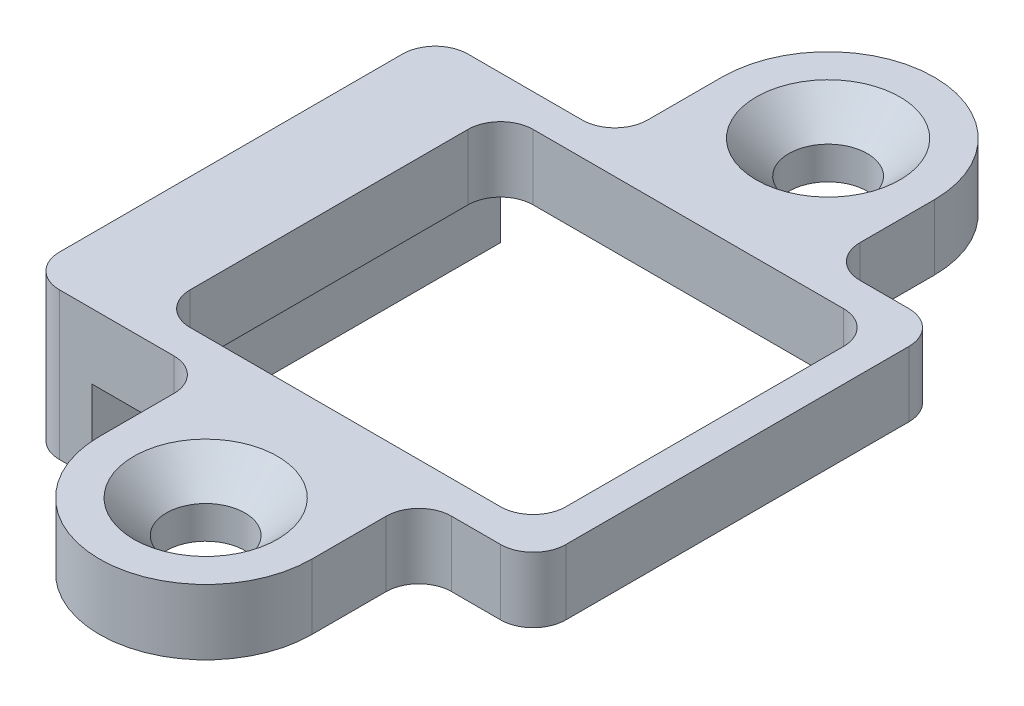
SolidWorks part; units mm, degrees
ref_plane "Front Plane" through (0, 0, 0) normal (0, 0, 1) x (1, 0, 0)
ref_plane "Top Plane" through (0, 0, 0) normal (0, 1, 0) x (1, 0, 0)
ref_plane "Right Plane" through (0, 0, 0) normal (1, 0, 0) x (0, 0, -1)
sketch "Sketch1" plane through (0, 0, 0) normal (0, 1, 0) x (1, 0, 0)
  line L0 (0, 9.525) -> (0, -9.525) construction
  line L1 (0, 9.525) -> (0, -9.525) construction
  line L2 (3.25, 9.525) -> (3.25, -9.525)
  line L3 (-3.25, 9.525) -> (-3.25, -9.525)
  line L4 (-6.75, 0) -> (6.75, 0) construction
  line L5 (6.75, 6.25) -> (-6.75, 6.25)
  line L6 (6.75, 6.25) -> (6.75, -6.25)
  line L7 (6.75, -6.25) -> (-6.75, -6.25)
  line L8 (-6.75, 6.25) -> (-6.75, -6.25)
  line L9 (3.25, 6.375) -> (-3.25, 6.375)
  line L10 (3.25, -6.375) -> (-3.25, -6.375)
  line L12 (-3.25, 6.25) -> (-8.75, 6.25)
  line L13 (-3.25, 6.25) -> (-3.25, -6.25)
  line L14 (-3.25, -6.25) -> (-8.75, -6.25)
  line L15 (-8.75, 6.25) -> (-8.75, -6.25)
  line L16 (5.75, 5.25) -> (-5.75, 5.25)
  line L17 (5.75, 5.25) -> (5.75, -5.25)
  line L18 (5.75, -5.25) -> (-5.75, -5.25)
  line L19 (-5.75, 5.25) -> (-5.75, -5.25)
  arc A0 (3.25, 9.525) -> (-3.25, 9.525) centre (0, 9.525) ccw
  arc A1 (-3.25, -9.525) -> (3.25, -9.525) centre (0, -9.525) ccw
  circle A2 centre (0, 9.525) radius 1.75
  circle A3 centre (0, -9.525) radius 1.75
  point P2 (0, 0)
  point P5 (0, 0)
  point P32 (5.75, 0)
  dimension "D2" = 3.25
  dimension "D6" = 3.5
  dimension "D7" = 3.5
  dimension "D1" = 19.05
  dimension "D3" = 13.5
  dimension "D4" = 12.5
  dimension "D5" = 6.75
  dimension "D8" = 0.125
  dimension "D9" = 2
  dimension "D10" = 1
  dimension "D11" = 1
  dimension "D12" = 1
extrude "Boss-Extrude1" add sketch "Sketch1" along normal blind 2 contours L16 L2 L5 L3 | L17 L18 L2 L7 L6 L5 L16 | L19 L16 L3 L5 L8 L7 L18 | L2 L18 L3 L7 | L3 A1 L2 L10 A3 | L2 A0 L3 L9 A2 | L12 L15 L14 L8 | A2 | A3 | L10 L2 L7 L3 | L2 L9 L3 L5 region at (3.1588, 0, -7.95) region at (0, 0, -6.3125) region at (5, 0, -6.1202) region at (0, 0, -5.75) region at (-3.3798, 0, -5.75) region at (0, 0, 5.75) region at (-7.75, 0, 0) region at (0, 0, 6.3125) region at (3.1588, 0, 7.95) region at (0, 0, -9.525) region at (0, 0, 9.525)
extrude "Boss-Extrude2" add sketch "Sketch1<4>" against normal blind 2.5 contours L12 L15 L14 L8 region at (-7.75, 0, 0)
sketch "Sketch1<4>" plane through (0, 0, 0) normal (0, 1, 0) x (1, 0, 0) same geometry as "Sketch1"
hole_wizard "CSK for M2 Flat Head Machine Screw2" positions "3DSketch2" profile "Sketch3" countersink size "M2" standard "ANSI Metric" end condition through all
sketch3d "3DSketch2"
  circle A2 centre (0, 0, 9.525) radius 1.75 construction
  circle A3 centre (0, 0, -9.525) radius 1.75 construction
  point P0 (0, 0, -9.525)
  point P3 (0, 0, 9.525)
  point P33 (0, 2, 9.525)
  point P35 (0, 2, -9.525)
  point P38 (0, 0, 0)
  point P47 (0, 1.75, 9.525)
  point P48 (0, 0, 0)
  point P51 (0, 1.75, -9.525)
sketch "Sketch3" plane through (0, 2, -9.525) normal (1, 0, 0) x (0, 0, 1)
  line L0 (0, 0) -> (0, 4.5)
  line L1 (0, 4.5) -> (1.2, 4.5)
  line L2 (1.2, 4.5) -> (1.2, 1)
  line L3 (1.2, 1) -> (2.2, 0)
  line L5 (2.2, 0) -> (0, 0)
  line L6 (-1.2, 1) -> (-2.2, 0) construction
  line L11 (0, -6.35) -> (0, 107.95) construction
  dimension "Thru Hole Dia." = 2.4
  dimension "Thru Hole Depth" = 4.5
  dimension "Near C'Sink Dia." = 4.4
  dimension "Near C'Sink Angle" = 90
fillet "Fillet1" radius 1 12 edges at (-8.75, -0.25, 6.25) (-8.75, -0.25, -6.25) (-3.25, 1, -6.25) (3.25, 1, -6.25) (3.25, 1, 6.25) (-3.25, 1, 6.25) (6.75, 1, 6.25) (6.75, 1, -6.25) (5.75, 1, -5.25) (-5.75, 1, -5.25) (5.75, 1, 5.25) (-5.75, 1, 5.25)
